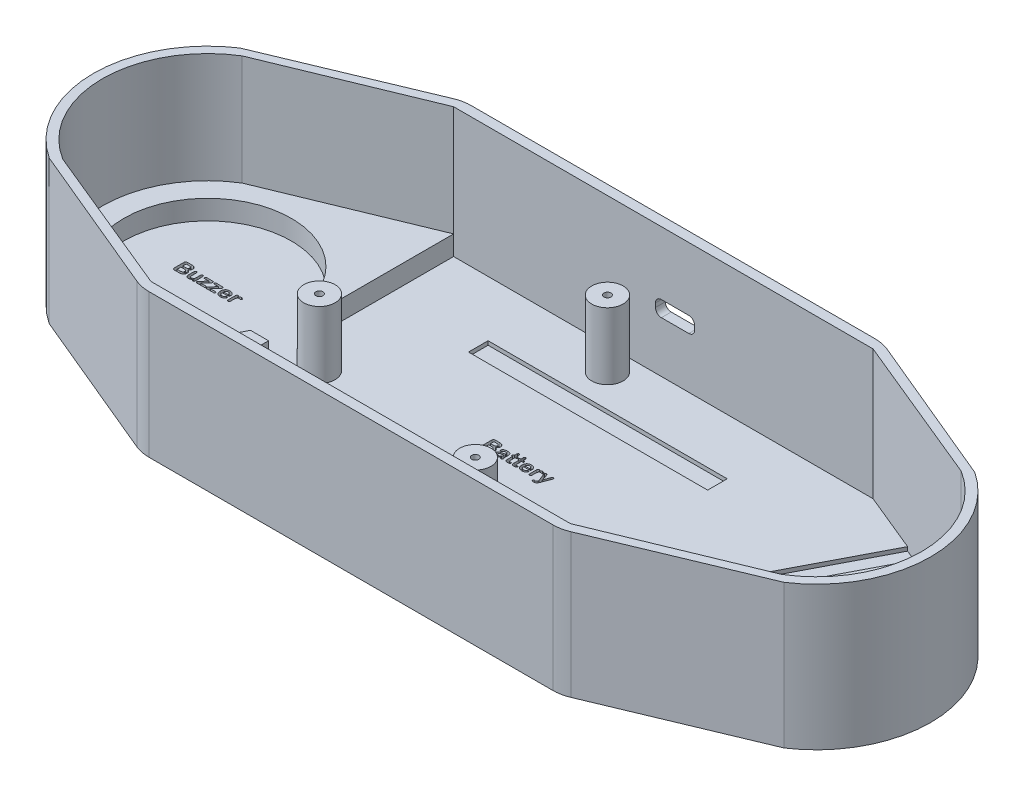
SolidWorks part; units mm, degrees
ref_plane "Front Plane" through (0, 0, 0) normal (0, 0, 1) x (1, 0, 0)
ref_plane "Top Plane" through (0, 0, 0) normal (0, 1, 0) x (1, 0, 0)
ref_plane "Right Plane" through (0, 0, 0) normal (1, 0, 0) x (0, 0, -1)
sketch "Sketch2" plane through (0, 0, 0) normal (0, 1, 0) x (1, 0, 0)
  line L0 (0, 0) -> (102, 0) construction
  line L1 (0, 0) -> (0, -77.2) construction
  line L2 (102, 0) -> (102, -77.2) construction
  line L3 (0, -77.2) -> (102, -77.2) construction
  line L4 (51, 0) -> (51, -77.2) construction
  line L5 (0, -38.6) -> (102, -38.6) construction
  line L6 (-2.5, 2.5) -> (104.5, 2.5)
  line L7 (-2.5, -79.7) -> (104.5, -79.7)
  line L8 (104.5, 2.5) -> (144.7372, -14.2911)
  line L9 (104.5, -79.7) -> (144.7372, -62.9089)
  line L10 (102, -38.6) -> (155.3, -38.6) construction
  line L11 (-2.5, -79.7) -> (-42.7372, -62.9089)
  line L12 (-2.5, 2.5) -> (-42.7372, -14.2911)
  line L13 (0, 0) -> (102, 0)
  line L14 (102, 0) -> (104.5, 0)
  line L15 (104.5, 0) -> (142.7026, -15.7437)
  line L16 (104.5, -77.2) -> (142.7026, -61.4563)
  line L17 (102, -77.2) -> (104.5, -77.2)
  line L18 (-2.5, -77.2) -> (-40.7026, -61.4563)
  line L19 (0, -77.2) -> (-2.5, -77.2)
  line L20 (-2.5, 0) -> (-40.7026, -15.7437)
  line L21 (0, 0) -> (-2.5, 0)
  line L22 (0, -77.2) -> (102, -77.2)
  line L23 (0, -76.7) -> (102, -76.7) construction
  line L24 (-2.5, -38.6) -> (-53.4807, -38.6) construction
  line L25 (-2.5, 0) -> (-2.5, -77.2) construction
  line L26 (104.5, 0) -> (104.5, -77.2) construction
  line L27 (0.5, 0) -> (0.5, -77.2) construction
  arc A0 (144.7372, -14.2911) -> (144.7372, -62.9089) centre (128.65, -38.6) cw
  arc A1 (-42.7372, -14.2911) -> (-42.7372, -62.9089) centre (-26.65, -38.6) ccw
  arc A2 (142.7026, -15.7437) -> (142.7026, -61.4563) centre (128.65, -38.6) cw
  arc A3 (-40.7026, -15.7437) -> (-40.7026, -61.4563) centre (-26.65, -38.6) ccw
  circle A4 centre (5.55, -71.7) radius 1.1
  circle A5 centre (5.6, -42.325) radius 1.1
  circle A6 centre (61.615, -58.575) radius 1.1
  circle A7 centre (42.614, -5.87) radius 1.1
  point P16 (157.8, -38.6)
  dimension "D3" = 2.5
  dimension "D10" = 2.5
  dimension "D11" = 5.05
  dimension "D12" = 5
  dimension "D13" = 34.375
  dimension "D15" = 18.125
  dimension "D17" = 42.114
  dimension "D1" = 77.2
  dimension "D2" = 102
  dimension "D4" = 2.5
  dimension "D5" = 2.5
  dimension "D6" = 2.5
  dimension "D7" = 0.5
  dimension "D8" = 2.5
  dimension "D9" = 53.3
  dimension "D14" = 5.1
  dimension "D16" = 61.115
  dimension "D18" = 70.83
  dimension "D19" = 0.5
extrude "MainExtrude" add sketch "Sketch2" along normal blind 33.1 contours A1 L11 L7 L9 A0 L8 L6 L12
extrude "MainCut" cut sketch "Sketch2<5>" along normal blind 50.8 contours L20 A3 L18 L19 L22 L17 L16 A2 L15 L14 L13 L21
sketch "Sketch2<5>" plane through (0, 0, 0) normal (0, 1, 0) x (1, 0, 0) same geometry as "Sketch2"
extrude "BassExtrude" add sketch "Sketch2<6>" against normal blind 3.5 contours L12 A1 L11 L7 L9 A0 L8 L6
sketch "Sketch2<6>" plane through (0, 0, 0) normal (0, 1, 0) x (1, 0, 0) same geometry as "Sketch2"
fillet "Fillet1" radius 10 4 edges at (104.5, 14.8, -2.5) (-2.5, 14.8, -2.5) (104.5, 14.8, 79.7) (-2.5, 14.8, 79.7)
sketch "Sketch6" plane through (0, 0, 0) normal (0, 1, 0) x (1, 0, 0)
  line L1 (-2.5, 0) -> (-2.5, -30)
  line L2 (-2.5, 0) -> (-2.5, -77.2) construction
  line L4 (-2.5, -77.2) -> (-2.5, -47.2)
  line L5 (-2.5, -47.2) -> (-52.065, -47.2) construction
  line L6 (-2.5, -30) -> (-52.065, -30) construction
  line L7 (-7.1001, -30) -> (-2.5, -30)
  line L8 (-2.5, -47.2) -> (-7.1001, -47.2)
  line L9 (-2.5, 0) -> (-40.7026, -15.7437)
  line L10 (-2.5, -77.2) -> (-40.7026, -61.4563)
  arc A2 (-40.7026, -15.7437) -> (-40.7026, -61.4563) centre (-26.65, -38.6) ccw
  arc A3 (-7.1001, -30) -> (-7.1001, -47.2) centre (-26.65, -38.6) ccw
  dimension "D1" = 30
  dimension "D2" = 30
extrude "Buzzer" add sketch "Sketch6" along normal blind 5
sketch "Sketch8" plane through (0, 0, 0) normal (0, 1, 0) x (1, 0, 0)
  text T0 "Buzzer" font "Arial Rounded MT Bold" height 3.5
  text T1 "Battery" font "Arial Rounded MT Bold" height 3.5
  text T2 "Speaker" font "Arial Rounded MT Bold" height 3.5
extrude "Text" cut sketch "Sketch8" against normal blind 1
sketch "Sketch9" plane through (0, 0, 0) normal (0, 1, 0) x (1, 0, 0)
  line L1 (104.5, -77.2) -> (104.5, -42.2)
  line L2 (104.5, 0) -> (104.5, -77.2) construction
  line L5 (104.5, -35) -> (109.5, -35)
  line L15 (104.5, -42.2) -> (109.5, -42.2)
  line L16 (109.5, -42.2) -> (109.5, -75.1394)
  line L17 (104.5, -77.2) -> (142.7026, -61.4563) construction
  line L18 (109.5, -75.1394) -> (104.5, -77.2)
  line L19 (109.5, -35) -> (123.6013, -7.8719)
  line L20 (104.5, 0) -> (142.7026, -15.7437) construction
  line L21 (104.5, -35) -> (119.4834, -6.1748)
  line L22 (142.7026, -15.7437) -> (104.5, 0) construction
  line L23 (119.4834, -6.1748) -> (123.6013, -7.8719)
  dimension "D3" = 5
  dimension "D2" = 35
  dimension "D4" = 5
sketch "Sketch10" plane through (0, 0, 0) normal (0, 1, 0) x (1, 0, 0)
  line L1 (20.5, -19.2) -> (81.5, -19.2)
  line L3 (20.5, -57.2) -> (51, -57.2)
  line L6 (20.5, -19.2) -> (20.5, -14.2)
  line L11 (20.5, -14.2) -> (81.5, -14.2)
  line L12 (81.5, -14.2) -> (81.5, -19.2)
  line L13 (20.5, -57.2) -> (20.5, -62.2)
  line L14 (20.5, -62.2) -> (51, -62.2)
  line L15 (51, -62.2) -> (51, -57.2)
  line L16 (51, 0) -> (51, -77.2) construction
  dimension "D1" = 0
  dimension "D2" = 5
  dimension "D3" = 38
  dimension "D4" = 61
  dimension "D5" = 5
  dimension "D6" = 30.5
extrude "Battery Cover Molds" cut sketch "Sketch10" against normal blind 1
sketch "Sketch11" plane through (0, 0, 0) normal (0, 1, 0) x (1, 0, 0)
  circle A0 centre (5.6, -42.325) radius 0.9
  circle A1 centre (5.6, -42.325) radius 4
  circle A2 centre (5.55, -71.7) radius 0.9
  circle A3 centre (5.55, -71.7) radius 4
  circle A4 centre (61.615, -58.575) radius 0.9
  circle A5 centre (61.615, -58.575) radius 4
  circle A6 centre (42.614, -5.87) radius 0.9
  circle A7 centre (42.614, -5.87) radius 4
extrude "PCB Offsets" add sketch "Sketch11" along normal blind 17
sketch "Sketch12" plane through (0, 0, -2.5) normal (0, 0, -1) x (-1, 0, 0)
  line L0 (-51, 0) -> (-51, 33.1) construction
  line L1 (2.5, 0) -> (-104.5, 0) construction
  line L2 (0.4972, 33.1) -> (-102.4972, 33.1) construction
  line L3 (-102.4972, 17) -> (0.4972, 17) construction
  line L4 (-102.4972, 33.1) -> (-102.4972, -3.5) construction
  line L5 (0.4972, -3.5) -> (0.4972, 33.1) construction
  line L8 (2.5, 0) -> (-104.5, 0) construction
  line L10 (-59, 17) -> (-49, 17)
  line L11 (-59, 17) -> (-59, 13)
  line L12 (-59, 13) -> (-49, 13)
  line L13 (-49, 17) -> (-49, 13)
  dimension "D1" = 17
  dimension "D2" = 4
  dimension "D3" = 10
  dimension "D4" = 2
extrude "USB" cut sketch "Sketch12" against normal up to next
fillet "Fillet2" radius 1.5 4 edges at (49, 13, -1.25) (59, 13, -1.25) (49, 17, -1.25) (59, 17, -1.25)
extrude "Cut-Extrude1" cut sketch "Sketch9" against normal blind 1
